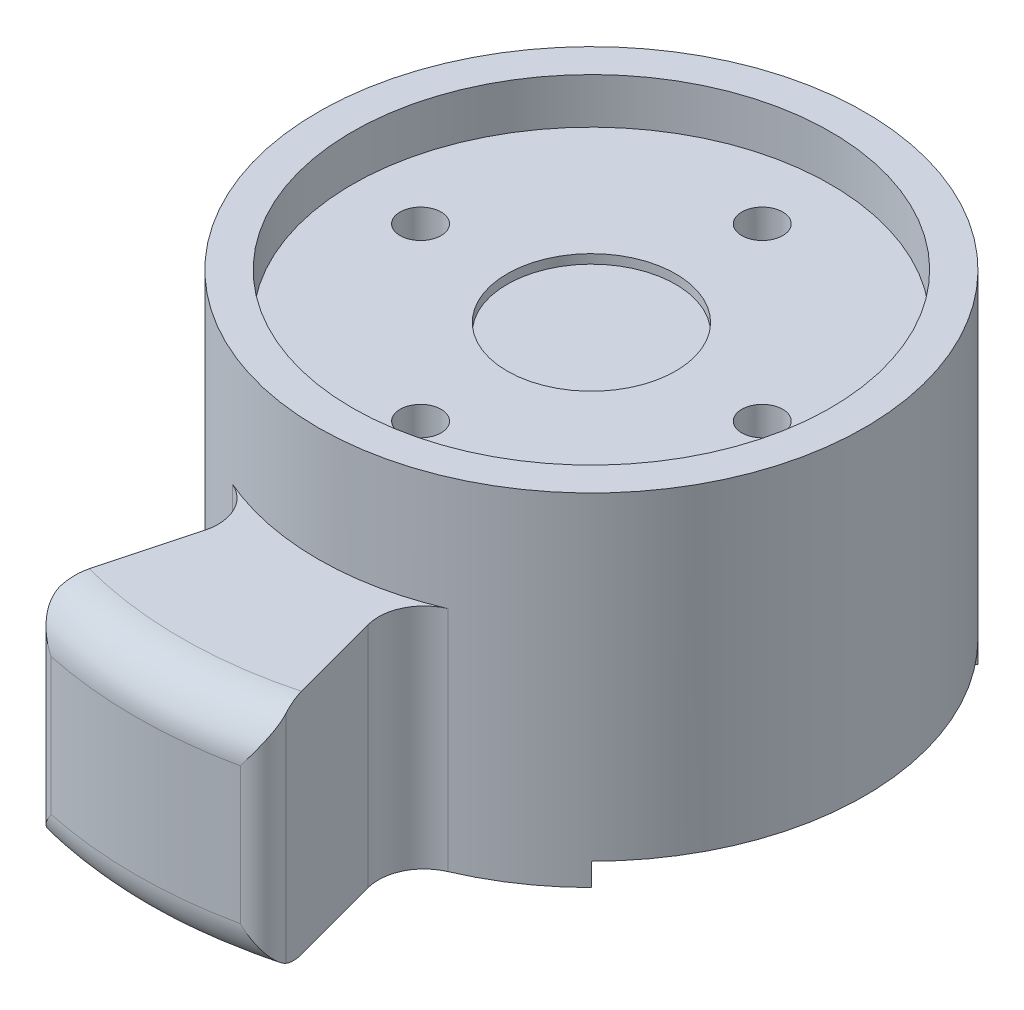
SolidWorks part; units mm, degrees
material "ABS"
ref_plane "Front" through (0, 0, 0) normal (0, 0, 1) x (1, 0, 0)
ref_plane "Top" through (0, 0, 0) normal (0, 1, 0) x (1, 0, 0)
ref_plane "Right" through (0, 0, 0) normal (1, 0, 0) x (0, 0, -1)
sketch "Szkic1" plane through (0, 0, 0) normal (0, 0, 1) x (1, 0, 0)
  line L0 (0, 12.6) -> (0, 0)
  line L4 (12, 1) -> (12, 15)
  line L5 (12, 15) -> (10.5, 15)
  line L6 (10.5, 15) -> (10.5, 13)
  line L7 (0, 0) -> (6, 0)
  line L8 (10.5, 13) -> (3.7, 13)
  line L9 (0, 12.6) -> (3.7, 12.6)
  line L10 (3.7, 12.6) -> (3.7, 13)
  line L29 (6, 0) -> (6, 1)
  line L30 (6, 1) -> (12, 1)
  dimension "D1" = 13
  dimension "D2" = 0.4
  dimension "D3" = 14
  dimension "D4" = 6
  dimension "D5" = 1
  dimension "D6" = 6
  dimension "D7" = 1.5
  dimension "D8" = 2
  dimension "D9" = 3.7
revolve "Obrót1" add sketch "Szkic1" angle 360 about L0
sketch "Szkic3" plane through (0, 1, 0) normal (0, -1, 0) x (1, 0, 0)
  line L0 (0, 0) -> (0, 12.6012) construction
  line L1 (-8.4853, -8.4853) -> (-4.2426, -4.2426)
  line L2 (8.4853, -8.4853) -> (4.2426, -4.2426)
  line L3 (-4.2426, 4.2426) -> (-8.4853, 8.4853)
  line L4 (4.2426, 4.2426) -> (8.4853, 8.4853)
  arc A0 (-4.2426, -4.2426) -> (4.2426, -4.2426) centre (0, 0) ccw
  arc A1 (-8.4853, -8.4853) -> (8.4853, -8.4853) centre (0, 0) ccw
  arc A2 (4.2426, 4.2426) -> (-4.2426, 4.2426) centre (0, 0) ccw
  arc A3 (8.4853, 8.4853) -> (-8.4853, 8.4853) centre (0, 0) ccw
  dimension "D1" = 45
extrude "Dodanie-wyciągnięcie1" add sketch "Szkic3" along normal blind 1
sketch "Szkic4" plane through (0, 0, 0) normal (0, 1, 0) x (1, 0, 0)
  line L0 (0, 0) -> (0, -24.3205) construction
  line L1 (3.1058, -11.5911) -> (5.1764, -19.3185)
  line L2 (-3.1058, -11.5911) -> (-5.1764, -19.3185)
  arc A0 (-5.1764, -19.3185) -> (5.1764, -19.3185) centre (0, 0) ccw
  arc A1 (-3.1058, -11.5911) -> (3.1058, -11.5911) centre (0, 0) ccw
  dimension "D1" = 40
  dimension "D2" = 15
extrude "Dodanie-wyciągnięcie2" add sketch "Szkic4" along normal blind 10
fillet "Zaokrąglenie1" radius 1 2 edges at (5.1764, 5, 19.3185) (-5.1764, 5, 19.3185)
fillet "Zaokrąglenie2" radius 2 2 edges at (-3.1058, 5, 11.5911) (3.1058, 5, 11.5911)
fillet "Zaokrąglenie3" radius 2 2 edges at (0, 0, 20) (0, 10, 20) tangent propagation no
sketch "Szkic5" plane through (0, 13, 0) normal (0, 1, 0) x (1, 0, 0)
  line L0 (0, 0) -> (0, 10.0639) construction
  circle A0 centre (0, 7.5) radius 0.9
  circle A1 centre (7.5, 0) radius 0.9
  circle A2 centre (0, -7.5) radius 0.9
  circle A3 centre (-7.5, 0) radius 0.9
  point P14 (0, 0)
  dimension "D1" = 7.5
  dimension "D2" = 1.8
  dimension "D3" = 4
extrude "Wytnij-wyciągnięcie1" cut sketch "Szkic5" against normal through all
